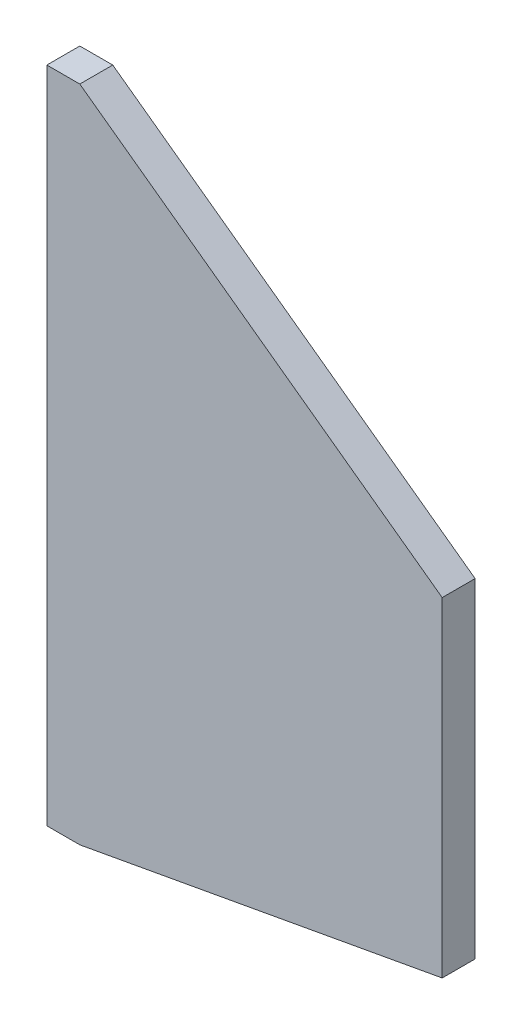
SolidWorks part; units mm, degrees
material "Beech"
ref_plane "Front Plane" through (0, 0, 0) normal (0, 0, 1) x (1, 0, 0)
ref_plane "Top Plane" through (0, 0, 0) normal (0, 1, 0) x (1, 0, 0)
ref_plane "Right Plane" through (0, 0, 0) normal (1, 0, 0) x (0, 0, -1)
sketch "Sketch2" plane through (0, 0, 0) normal (0, 0, 1) x (1, 0, 0)
  line L0 (0, 0) -> (5.08, 0)
  line L1 (5.08, 0) -> (60.96, 10.16)
  line L2 (60.96, 10.16) -> (60.96, 60.96)
  line L3 (60.96, 60.96) -> (5.08, 101.6)
  line L4 (5.08, 101.6) -> (0, 101.6)
  line L5 (0, 101.6) -> (0, 0)
  point P3 (0, 0)
  dimension "D1" = 101.6
  dimension "D2" = 60.96
  dimension "D3" = 50.8
  dimension "D4" = 40.64
  dimension "D5" = 5.08
extrude "Boss-Extrude1" add sketch "Sketch2" along normal blind 5.08
